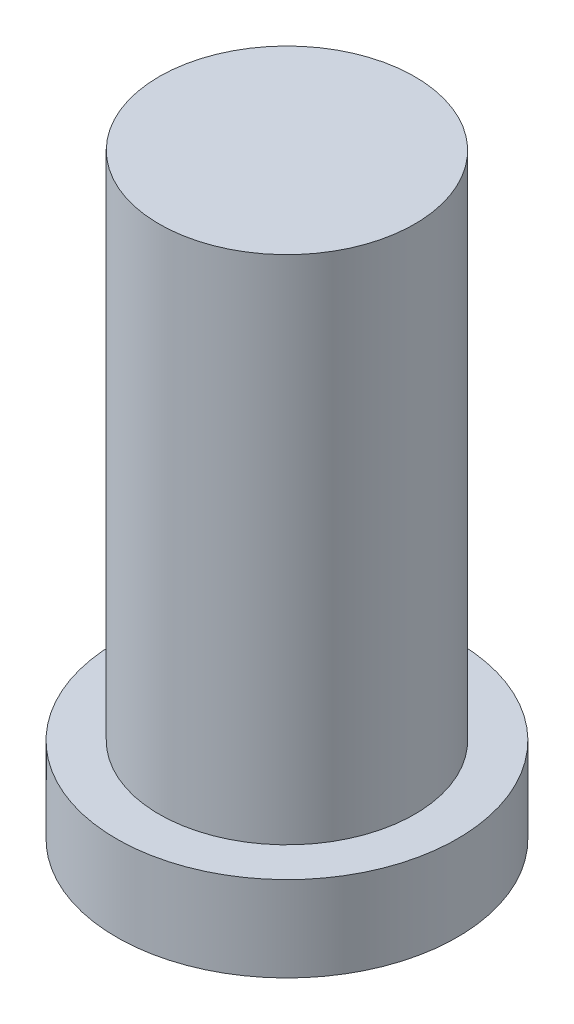
SolidWorks part; units mm, degrees
material "K110"
ref_plane "Front Plane" through (0, 0, 0) normal (0, 0, 1) x (1, 0, 0)
ref_plane "Top Plane" through (0, 0, 0) normal (0, 1, 0) x (1, 0, 0)
ref_plane "Right Plane" through (0, 0, 0) normal (1, 0, 0) x (0, 0, -1)
sketch "Sketch1" plane through (0, 0, 0) normal (0, 0, 1) x (1, 0, 0)
  line L0 (0, 0) -> (10, 0)
  line L1 (10, 0) -> (10, 5)
  line L2 (10, 5) -> (7.5, 5)
  line L3 (7.5, 5) -> (7.5, 35)
  line L4 (7.5, 35) -> (0, 35)
  line L5 (0, 35) -> (0, 0)
  line L6 (0, 40) -> (0, -5) construction
  point P9 (8.75, 5)
  dimension "D1" = 5
  dimension "D2" = 5
  dimension "D3" = 20
  dimension "D4" = 15
  dimension "D5" = 5
  dimension "D6" = 30
revolve "Revolve1" add sketch "Sketch1" angle 360 about L6
